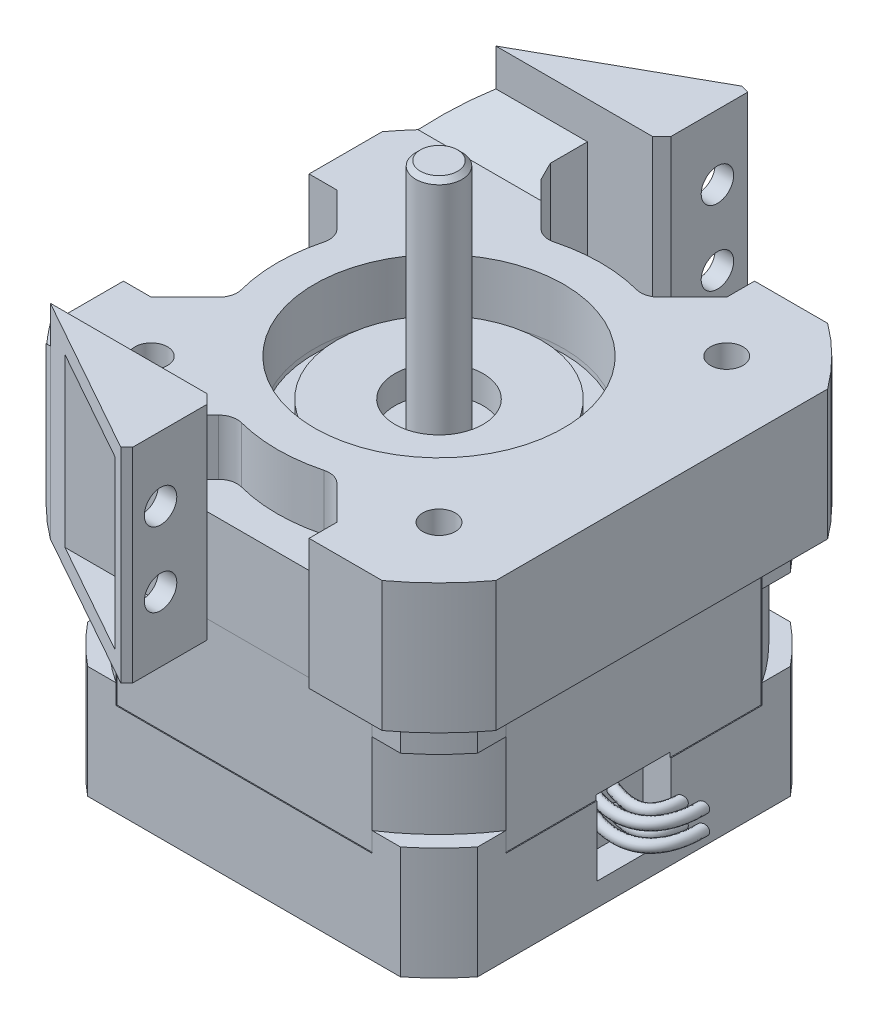
SolidWorks part; units mm, degrees
ref_plane "Front Plane" through (0, 0, 0) normal (0, 0, 1) x (1, 0, 0)
ref_plane "Top Plane" through (0, 0, 0) normal (0, 1, 0) x (1, 0, 0)
ref_plane "Right Plane" through (0, 0, 0) normal (1, 0, 0) x (0, 0, -1)
sketch "Sketch1" plane through (0, 0, 0) normal (0, 1, 0) x (1, 0, 0)
  line L0 (0, -21) -> (0, 21) construction
  line L1 (-21, 16.851) -> (-21, -16.851)
  line L2 (-16.851, -21) -> (16.851, -21)
  line L3 (21, -16.851) -> (21, 16.851)
  line L4 (16.851, 21) -> (-16.851, 21)
  line L5 (-21, 0) -> (21, 0) construction
  arc A0 (-21, 16.851) -> (-16.851, 21) centre (0, 0) cw
  arc A1 (16.851, 21) -> (21, 16.851) centre (0, 0) cw
  arc A2 (21, -16.851) -> (16.851, -21) centre (0, 0) cw
  arc A3 (-21, -16.851) -> (-16.851, -21) centre (0, 0) ccw
  dimension "D3" = 26.925
  dimension "D1" = 42
  dimension "D2" = 42
extrude "Boss-Extrude2" add sketch "Sketch1" along normal blind 33
sketch "Sketch3" plane through (0, 0, 0) normal (0, 0, 1) x (1, 0, 0)
  line L0 (0, -2.0131) -> (0, 34.8611) construction
  line L1 (-30.125, 20.875) -> (-25.125, 20.875)
  line L2 (-30.125, 20.875) -> (-30.125, 12.125)
  line L3 (-30.125, 12.125) -> (-25.125, 12.125)
  line L4 (-25.125, 20.875) -> (-25.125, 12.125)
  line L5 (21, 16.5) -> (-21, 16.5) construction
  line L6 (21, 33) -> (21, 0) construction
  line L7 (-21, 33) -> (-21, 0) construction
  point P13 (-25.125, 16.5)
  dimension "D1" = 8.75
  dimension "D2" = 25.125
  dimension "D3" = 5
revolve "Cut-Revolve1" cut sketch "Sketch3" angle 360 about L0
sketch "Sketch4" plane through (0, 33, 0) normal (0, 1, 0) x (1, 0, 0)
  circle A0 centre (0, 0) radius 13.425
  dimension "D1" = 26.85
extrude "Cut-Extrude1" cut sketch "Sketch4" against normal blind 0.5
sketch "Sketch5" plane through (0, 32.5, 0) normal (0, 1, 0) x (1, 0, 0)
  circle A0 centre (0, 0) radius 11
  dimension "D1" = 22
extrude "Boss-Extrude3" add sketch "Sketch5" along normal blind 2.5
sketch "Sketch6" plane through (0, 35, 0) normal (0, 1, 0) x (1, 0, 0)
  circle A0 centre (0, 0) radius 4.75
  dimension "D1" = 9.5
extrude "Cut-Extrude2" cut sketch "Sketch6" against normal blind 3
sketch "Sketch7" plane through (0, 32, 0) normal (0, 1, 0) x (1, 0, 0)
  circle A0 centre (0, 0) radius 2.5
  dimension "D1" = 5
extrude "Boss-Extrude4" add sketch "Sketch7" along normal blind 25.25
chamfer "Chamfer1" distance 0.5 angle 45 1 edges at (0, 57.25, 2.5)
sketch "Sketch8" plane through (0, 0, 0) normal (0, -1, 0) x (1, 0, 0)
  circle A0 centre (0, 0) radius 4.5
  dimension "D1" = 9
extrude "Cut-Extrude3" cut sketch "Sketch8" against normal blind 3
sketch "Sketch9" plane through (0, 33, 0) normal (0, 1, 0) x (1, 0, 0)
  line L0 (-15.5, 15.5) -> (15.5, 15.5) construction
  line L1 (15.5, 15.5) -> (15.5, -15.5) construction
  line L2 (15.5, -15.5) -> (-15.5, -15.5) construction
  line L3 (-15.5, -15.5) -> (-15.5, 15.5) construction
  point P2 (-15.5, 0)
  point P5 (0, 15.5)
  dimension "D1" = 31
  dimension "D2" = 31
hole_wizard "M3x0.5 Tapped Hole1" positions "Sketch11" profile "Sketch10" tap size "M3x0.5" standard "ANSI Metric"
sketch "Sketch11" plane through (0, 33, 0) normal (0, 1, 0) x (1, 0, 0)
  point P0 (-15.5, -15.5)
  point P3 (-15.5, 15.5)
  point P6 (15.5, 15.5)
  point P9 (15.5, -15.5)
sketch "Sketch10" plane through (-15.5, 33, 15.5) normal (1, 0, 0) x (0, 0, 1)
  line L0 (0, 0) -> (0, 5.2511)
  line L1 (0, 5.2511) -> (1.25, 4.5)
  line L2 (1.25, 4.5) -> (1.25, 0)
  line L5 (1.25, 0) -> (0, 0)
  line L10 (0, 5.2511) -> (-1.25, 4.5) construction
  line L11 (0, -6.35) -> (0, 107.95) construction
  dimension "Tap Drill Dia." = 2.5
  dimension "Tap Drill Depth" = 4.5
  dimension "Drill Angle" = 118
sketch "Sketch12" plane through (21, 0, 0) normal (1, 0, 0) x (0, 0, -1)
  line L0 (-16.851, 0) -> (16.851, 0) construction
  line L1 (-4, 10.5) -> (4, 10.5)
  line L2 (-4, 10.5) -> (-4, 2.5)
  line L3 (-4, 2.5) -> (4, 2.5)
  line L4 (4, 10.5) -> (4, 2.5)
  point P4 (0, 2.5)
  dimension "D1" = 8
  dimension "D2" = 8
  dimension "D3" = 2.5
extrude "Cut-Extrude4" cut sketch "Sketch12" against normal blind 3
sketch "Sketch13" plane through (18, 0, 0) normal (1, 0, 0) x (0, 0, -1)
  circle A0 centre (-1.1125, 7.415) radius 0.6
  circle A1 centre (0.707, 7.415) radius 0.6
  circle A2 centre (-1.1125, 5.3322) radius 0.6
  circle A3 centre (0.707, 5.3322) radius 0.6
  dimension "D1" = 1.2
sketch "Sketch14" plane through (0, 0, 0) normal (0, 1, 0) x (1, 0, 0)
  spline S0 degree 2 poles (17.6767, 0) (23.6461, -2.3668) (23.7984, 3.3576) knots 0 0 0 1 1 1
sweep "Sweep2" add profiles "Sketch13" path "Sketch14"
sketch "Sketch15" plane through (0, 0, -21) normal (0, 0, -1) x (-1, 0, 0)
  line L0 (-13.7937, 12.125) -> (-13.7937, 20.875) construction
  line L1 (-13.7937, 23) -> (13.7937, 23)
  line L2 (-13.7937, 23) -> (-13.7937, 10)
  line L3 (-13.7937, 10) -> (13.7937, 10)
  line L4 (13.7937, 23) -> (13.7937, 10)
  line L5 (13.7937, 20.875) -> (13.7937, 12.125) construction
  point P8 (-13.7937, 16.5)
  point P9 (-13.7937, 16.5)
  dimension "D1" = 13
extrude "Cut-Extrude5" cut sketch "Sketch15" against normal blind 0.1
ref_axis "Axis1" through (0, 0, 0) along (0, 1, 0)
pattern_circular "CirPattern1" count 4 over 360 about axis through (0, 0, 0) along (0, 1, 0) of "Cut-Extrude5"
ref_plane "Plane1" through (0, 33, 0) normal (0, 1, 0) x (1, 0, 0)
sketch "Sketch16" plane through (0, 33, 0) normal (0, 1, 0) x (1, 0, 0)
  line L0 (-10.001, -21) -> (-5.5264, -16.5254)
  line L1 (9.999, -21) -> (5.5249, -16.5259)
  line L2 (-21, -9.999) -> (-16.5259, -5.5249)
  line L3 (-16.5254, 5.5264) -> (-21, 10.001)
  line L4 (-21, 16.851) -> (-21, -16.851)
  line L5 (-16.851, -21) -> (16.851, -21)
  line L6 (21, -16.851) -> (21, 16.851)
  line L7 (16.851, 21) -> (-16.851, 21)
  line L8 (-21, 16.851) -> (-21, -16.851)
  line L9 (-16.851, -21) -> (16.851, -21)
  line L10 (21, -16.851) -> (21, 16.851)
  line L11 (16.851, 21) -> (-16.851, 21)
  line L12 (-10.001, 21) -> (-5.5264, 16.5254)
  line L13 (9.999, 21) -> (5.5249, 16.5259)
  circle A0 centre (0, 0) radius 13.425 construction
  circle A1 centre (0, 0) radius 13.425
  arc A4 (-16.851, 21) -> (-21, 16.851) centre (0, 0) ccw
  arc A5 (-21, -16.851) -> (-16.851, -21) centre (0, 0) ccw
  arc A6 (16.851, -21) -> (21, -16.851) centre (0, 0) ccw
  arc A7 (21, 16.851) -> (16.851, 21) centre (0, 0) ccw
  arc A8 (-16.851, 21) -> (-21, 16.851) centre (0, 0) ccw
  arc A9 (-21, -16.851) -> (-16.851, -21) centre (0, 0) ccw
  arc A10 (16.851, -21) -> (21, -16.851) centre (0, 0) ccw
  arc A11 (21, 16.851) -> (16.851, 21) centre (0, 0) ccw
  circle A12 centre (-15.5, -15.5) radius 1.25 construction
  circle A13 centre (15.5, -15.5) radius 1.25 construction
  circle A14 centre (15.5, 15.5) radius 1.25 construction
  circle A15 centre (-15.5, 15.5) radius 1.25 construction
  circle A16 centre (-15.5, -15.5) radius 1.25
  circle A17 centre (15.5, -15.5) radius 1.25
  circle A18 centre (15.5, 15.5) radius 1.25
  circle A19 centre (-15.5, 15.5) radius 1.25
  circle A20 centre (-15.5, 15.5) radius 1.75
  circle A21 centre (-15.5, -15.5) radius 1.75
  circle A22 centre (15.5, -15.5) radius 1.75
  circle A23 centre (15.5, 15.5) radius 1.75
  circle A24 centre (0, 0) radius 17.425
  dimension "D4" = 20
  dimension "D5" = 45
  dimension "D6" = 45
  dimension "D7" = 6.85
  dimension "D8" = 45
  dimension "D9" = 45
  dimension "D10" = 20
  dimension "D11" = 6.85
  dimension "D12" = 45
  dimension "D13" = 45
  dimension "D14" = 20
  dimension "D15" = 6.85
  dimension "D1" = 0
  dimension "D2" = 0.5
  dimension "D3" = 4
extrude "Boss-Extrude5" add sketch "Sketch16" along normal blind 6 separate body contours A24 L2 L8 A9 L9 L0 A21 | A24 A1 | A24 L12 L11 A8 L8 L3 A20 | A24 L1 L9 A10 L10 A11 L11 L13 A23 A22 region at (-13.426, 33, 20.7812) region at (-11.9734, 33, 11.9723) region at (8.0785, 33, 18.4465) region at (-18.608, 33, -7.9184)
sketch "Sketch17" plane through (0, 39, 0) normal (0, 1, 0) x (1, 0, 0)
  line L13 (-21, 10.001) -> (-24, 10.001)
  line L14 (-10.001, 21) -> (-10.001, 24)
  line L15 (9.999, 21) -> (9.999, 24)
  line L16 (-21, -9.999) -> (-24, -9.999)
  line L17 (-10.001, -21) -> (-10.001, -24)
  line L18 (9.999, -21) -> (9.999, -24)
  line L26 (-8.7583, -24) -> (-4.6476, -19.8892)
  line L27 (4.646, -19.8896) -> (8.7564, -24)
  line L28 (8.7564, -24) -> (17.8747, -24)
  line L29 (24, -17.8747) -> (24, 17.8747)
  line L30 (17.8747, 24) -> (8.7564, 24)
  line L31 (8.7564, 24) -> (4.646, 19.8896)
  line L32 (-4.6476, 19.8892) -> (-8.7583, 24)
  line L33 (-8.7583, 24) -> (-17.8747, 24)
  line L34 (-24, 17.8747) -> (-24, 8.7583)
  line L35 (-24, 8.7583) -> (-19.8892, 4.6476)
  line L36 (-19.8896, -4.646) -> (-24, -8.7564)
  line L37 (-24, -8.7564) -> (-24, -17.8747)
  line L38 (-17.8747, -24) -> (-8.7583, -24)
  line L39 (-8.7583, -24) -> (-4.6476, -19.8892)
  line L40 (4.646, -19.8896) -> (8.7564, -24)
  line L41 (8.7564, -24) -> (17.8747, -24)
  line L42 (24, -17.8747) -> (24, 17.8747)
  line L43 (17.8747, 24) -> (8.7564, 24)
  line L44 (8.7564, 24) -> (4.646, 19.8896)
  line L45 (-4.6476, 19.8892) -> (-8.7583, 24)
  line L46 (-8.7583, 24) -> (-17.8747, 24)
  line L47 (-24, 17.8747) -> (-24, 8.7583)
  line L48 (-24, 8.7583) -> (-19.8892, 4.6476)
  line L49 (-19.8896, -4.646) -> (-24, -8.7564)
  line L50 (-24, -8.7564) -> (-24, -17.8747)
  line L51 (-17.8747, -24) -> (-8.7583, -24)
  line L71 (-9.7939, -21.5) -> (-5.3895, -17.0956)
  line L72 (5.388, -17.0961) -> (9.7919, -21.5)
  line L73 (9.7919, -21.5) -> (17.0259, -21.5)
  line L74 (21.5, -17.0259) -> (21.5, 17.0259)
  line L75 (17.0259, 21.5) -> (9.7919, 21.5)
  line L76 (9.7919, 21.5) -> (5.388, 17.0961)
  line L77 (-5.3895, 17.0956) -> (-9.7939, 21.5)
  line L78 (-9.7939, 21.5) -> (-17.0259, 21.5)
  line L79 (-21.5, 17.0259) -> (-21.5, 9.7939)
  line L80 (-21.5, 9.7939) -> (-17.0956, 5.3895)
  line L81 (-17.0961, -5.388) -> (-21.5, -9.7919)
  line L82 (-21.5, -9.7919) -> (-21.5, -17.0259)
  line L83 (-17.0259, -21.5) -> (-9.7939, -21.5)
  line L84 (-9.7939, -21.5) -> (-5.3895, -17.0956)
  line L85 (5.388, -17.0961) -> (9.7919, -21.5)
  line L86 (9.7919, -21.5) -> (17.0259, -21.5)
  line L87 (21.5, -17.0259) -> (21.5, 17.0259)
  line L88 (17.0259, 21.5) -> (9.7919, 21.5)
  line L89 (9.7919, 21.5) -> (5.388, 17.0961)
  line L90 (-5.3895, 17.0956) -> (-9.7939, 21.5)
  line L91 (-9.7939, 21.5) -> (-17.0259, 21.5)
  line L92 (-21.5, 17.0259) -> (-21.5, 9.7939)
  line L93 (-21.5, 9.7939) -> (-17.0956, 5.3895)
  line L94 (-17.0961, -5.388) -> (-21.5, -9.7919)
  line L95 (-21.5, -9.7919) -> (-21.5, -17.0259)
  line L96 (-17.0259, -21.5) -> (-9.7939, -21.5)
  arc A14 (-4.6476, -19.8892) -> (4.646, -19.8896) centre (0, 0) ccw
  arc A15 (17.8747, -24) -> (24, -17.8747) centre (0, 0) ccw
  arc A16 (24, 17.8747) -> (17.8747, 24) centre (0, 0) ccw
  arc A17 (4.646, 19.8896) -> (-4.6476, 19.8892) centre (0, 0) ccw
  arc A18 (-17.8747, 24) -> (-24, 17.8747) centre (0, 0) ccw
  arc A19 (-19.8892, 4.6476) -> (-19.8896, -4.646) centre (0, 0) ccw
  arc A20 (-24, -17.8747) -> (-17.8747, -24) centre (0, 0) ccw
  arc A21 (-4.6476, -19.8892) -> (4.646, -19.8896) centre (0, 0) ccw
  arc A22 (17.8747, -24) -> (24, -17.8747) centre (0, 0) ccw
  arc A23 (24, 17.8747) -> (17.8747, 24) centre (0, 0) ccw
  arc A24 (4.646, 19.8896) -> (-4.6476, 19.8892) centre (0, 0) ccw
  arc A25 (-17.8747, 24) -> (-24, 17.8747) centre (0, 0) ccw
  arc A26 (-19.8892, 4.6476) -> (-19.8896, -4.646) centre (0, 0) ccw
  arc A27 (-24, -17.8747) -> (-17.8747, -24) centre (0, 0) ccw
  arc A36 (-5.3895, -17.0956) -> (5.388, -17.0961) centre (0, 0) ccw
  arc A37 (17.0259, -21.5) -> (21.5, -17.0259) centre (0, 0) ccw
  arc A38 (21.5, 17.0259) -> (17.0259, 21.5) centre (0, 0) ccw
  arc A39 (5.388, 17.0961) -> (-5.3895, 17.0956) centre (0, 0) ccw
  arc A40 (-17.0259, 21.5) -> (-21.5, 17.0259) centre (0, 0) ccw
  arc A41 (-17.0956, 5.3895) -> (-17.0961, -5.388) centre (0, 0) ccw
  arc A42 (-21.5, -17.0259) -> (-17.0259, -21.5) centre (0, 0) ccw
  arc A43 (-5.3895, -17.0956) -> (5.388, -17.0961) centre (0, 0) ccw
  arc A44 (17.0259, -21.5) -> (21.5, -17.0259) centre (0, 0) ccw
  arc A45 (21.5, 17.0259) -> (17.0259, 21.5) centre (0, 0) ccw
  arc A46 (5.388, 17.0961) -> (-5.3895, 17.0956) centre (0, 0) ccw
  arc A47 (-17.0259, 21.5) -> (-21.5, 17.0259) centre (0, 0) ccw
  arc A48 (-17.0956, 5.3895) -> (-17.0961, -5.388) centre (0, 0) ccw
  arc A49 (-21.5, -17.0259) -> (-17.0259, -21.5) centre (0, 0) ccw
  line M24 (9.999, -21) -> (16.851, -21)
  arc M25 (16.851, -21) -> (21, -16.851) centre (0, 0) ccw
  line M26 (21, -16.851) -> (21, 16.851)
  arc M27 (21, 16.851) -> (16.851, 21) centre (0, 0) ccw
  line M28 (16.851, 21) -> (9.999, 21)
  line M32 (-10.001, 21) -> (-16.851, 21)
  arc M33 (-16.851, 21) -> (-21, 16.851) centre (0, 0) ccw
  line M34 (-21, 16.851) -> (-21, 10.001)
  line M38 (-21, -9.999) -> (-21, -16.851)
  arc M39 (-21, -16.851) -> (-16.851, -21) centre (0, 0) ccw
  line M40 (-16.851, -21) -> (-10.001, -21)
  dimension "D1" = 3
  dimension "D2" = 0.5
extrude "Boss-Extrude6" add sketch "Sketch17" against normal blind 14 separate body contours L46 A25 L47 L13 L14 M34 M33 M32 | L50 A27 L51 L17 L16 M40 M39 M38 | L42 A23 L43 L15 L18 L41 A22 M28 M27 M26 M25 M24 region at (-22.75, 39, -10.199) region at (-21.698, 39, 13.5124) region at (10.499, 39, -22.75)
fillet "Fillet1" radius 2 6 edges at (5.5249, 36, 16.5259) (-5.5264, 36, 16.5254) (-16.5259, 36, 5.5249) (-16.5254, 36, -5.5264) (5.5249, 36, -16.5259) (-5.5264, 36, -16.5254)
extrude "Boss-Extrude7" add sketch "Sketch17<4>" against normal up to vertex (6 mm away) separate body contours L95 A49 L96 L17 L16 M40 M39 M38 | L91 A47 L92 L13 L14 M34 M33 M32 | L87 A45 L88 L15 L18 L86 A44 M28 M27 M26 M25 M24 region at (-21.25, 39, -10.1636) region at (-21.25, 39, 10.1617) region at (13.5124, 39, -21.0549) up to point (-17.3686, 33, 6.3676)
sketch "Sketch17<4>" plane through (0, 39, 0) normal (0, 1, 0) x (1, 0, 0) same geometry as "Sketch17"
combine bodies "Combine2" operation type add bodies to combine 115 122 121 114 116 117 120
sketch "Sketch18" plane through (0, 39, 0) normal (0, 1, 0) x (1, 0, 0)
  line L0 (-10.001, 24) -> (-0.001, 24)
  line L1 (-0.001, 24) -> (-0.001, 34)
  line L3 (-17.8747, 24) -> (-0.001, 34)
  line L4 (-17.8747, -24) -> (-0.001, -24)
  line L5 (-10.001, -21) -> (-10.001, -24) construction
  line L6 (-0.001, -24) -> (-0.001, -34)
  line L7 (-0.001, -34) -> (-17.8747, -24)
  line L23 (9.999, 24) -> (9.999, 21)
  line L24 (9.999, 21) -> (6.3676, 17.3686)
  line L25 (-6.3692, 17.3682) -> (-10.001, 21)
  line L26 (-10.001, 21) -> (-10.001, 24)
  line L27 (-10.001, 24) -> (-17.8747, 24)
  line L28 (-24, 17.8747) -> (-24, 10.001)
  line L29 (-24, 10.001) -> (-21, 10.001)
  line L30 (-21, 10.001) -> (-17.3682, 6.3692)
  line L31 (-17.3686, -6.3676) -> (-21, -9.999)
  line L32 (-21, -9.999) -> (-24, -9.999)
  line L33 (-24, -9.999) -> (-24, -17.8747)
  line L34 (-17.8747, -24) -> (-10.001, -24)
  line L35 (-10.001, -24) -> (-10.001, -21)
  line L36 (-10.001, -21) -> (-6.3692, -17.3682)
  line L37 (6.3676, -17.3686) -> (9.999, -21)
  line L38 (9.999, -21) -> (9.999, -24)
  line L39 (9.999, -24) -> (17.8747, -24)
  line L40 (24, -17.8747) -> (24, 17.8747)
  line L41 (17.8747, 24) -> (9.999, 24)
  line L46 (-10.001, 24) -> (-17.8747, 24)
  arc A15 (4.4434, 16.8489) -> (6.3676, 17.3686) centre (4.9534, 18.7828) ccw
  arc A16 (4.4434, 16.8489) -> (-4.4448, 16.8486) centre (0, 0) ccw
  arc A17 (-6.3692, 17.3682) -> (-4.4448, 16.8486) centre (-4.955, 18.7824) ccw
  arc A18 (-17.8747, 24) -> (-24, 17.8747) centre (0, 0) ccw
  arc A19 (-16.8486, 4.4448) -> (-17.3682, 6.3692) centre (-18.7824, 4.955) ccw
  arc A20 (-16.8486, 4.4448) -> (-16.8489, -4.4434) centre (0, 0) ccw
  arc A21 (-17.3686, -6.3676) -> (-16.8489, -4.4434) centre (-18.7828, -4.9534) ccw
  arc A22 (-24, -17.8747) -> (-17.8747, -24) centre (0, 0) ccw
  arc A23 (-4.4448, -16.8486) -> (-6.3692, -17.3682) centre (-4.955, -18.7824) ccw
  arc A24 (-4.4448, -16.8486) -> (4.4434, -16.8489) centre (0, 0) ccw
  arc A25 (6.3676, -17.3686) -> (4.4434, -16.8489) centre (4.9534, -18.7828) ccw
  arc A26 (17.8747, -24) -> (24, -17.8747) centre (0, 0) ccw
  arc A27 (24, 17.8747) -> (17.8747, 24) centre (0, 0) ccw
  dimension "D3" = 10
  dimension "D1" = 10
  dimension "D2" = 10
  dimension "D4" = 10
  dimension "D5" = 0
extrude "Boss-Extrude8" add sketch "Sketch18" against normal up to surface (14 mm away) up to face at (-18.2819, 25, -18.2819)
sketch "Sketch19" plane through (-0.001, 0, 0) normal (1, 0, 0) x (0, 0, -1)
  line L0 (34, 25) -> (34, 39) construction
  line L1 (34, 27) -> (26, 27)
  line L2 (34, 27) -> (34, 37)
  line L3 (34, 37) -> (26, 37)
  line L4 (26, 27) -> (26, 37)
  line L5 (24, 39) -> (34, 39) construction
  line L6 (-34, 25) -> (-34, 39) construction
  line L7 (-34, 37) -> (-26, 37)
  line L8 (-34, 37) -> (-34, 27)
  line L9 (-34, 27) -> (-26, 27)
  line L10 (-26, 37) -> (-26, 27)
  line L11 (-34, 39) -> (-24, 39) construction
  circle A0 centre (30, 32) radius 1.75
  circle A1 centre (-30, 32) radius 1.75
  point P19 (34, 32)
  point P20 (-34, 32)
  point P21 (30, 27)
  point P25 (-30, 27)
  dimension "D7" = 3.5
  dimension "D8" = 3.5
  dimension "D1" = 10
  dimension "D2" = 2
  dimension "D3" = 8
  dimension "D4" = 8
  dimension "D5" = 10
  dimension "D6" = 2
ref_plane "Plane2" through (-2.001, 0, 0) normal (1, 0, 0) x (0, 0, -1)
sketch "Sketch20" plane through (-2.001, 0, 0) normal (1, 0, 0) x (0, 0, -1)
  line L0 (34, 27) -> (34, 37) construction
  line L1 (34, 37) -> (26, 37) construction
  line L2 (34, 27) -> (26, 27) construction
  line L3 (26, 27) -> (26, 37) construction
  line L4 (-34, 37) -> (-34, 27) construction
  line L5 (-34, 37) -> (-26, 37) construction
  line L6 (-26, 37) -> (-26, 27) construction
  line L7 (-34, 27) -> (-26, 27) construction
  line L8 (34, 27) -> (34, 37)
  line L9 (34, 37) -> (26, 37)
  line L10 (34, 27) -> (26, 27)
  line L11 (26, 27) -> (26, 37)
  line L12 (-34, 37) -> (-34, 27)
  line L13 (-34, 37) -> (-26, 37)
  line L14 (-26, 37) -> (-26, 27)
  line L15 (-34, 27) -> (-26, 27)
  circle A0 centre (-30, 32) radius 1.75 construction
  circle A1 centre (30, 32) radius 1.75 construction
  circle A2 centre (-30, 32) radius 1.75
  circle A3 centre (30, 32) radius 1.75
extrude "Cut-Extrude7" cut sketch "Sketch20" against normal blind 34 contours L12 L15 L14 L13 A2 | A2 | L10 L11 L9 L8 region at (-2.001, 36.8719, 30)
chamfer "Chamfer2" distance 2 angle 45 2 edges at (-10.001, 32, 24) (-10.001, 32, -24)
ref_plane "Plane3" [suppressed] through (-2.001, 37, 32.881) normal (0, 0, 1) x (1, 0, 0)
extrude "Cut-Extrude10" cut sketch "Sketch19" against normal blind 10 contours A0 | A1
sketch "Sketch21" plane through (0, 39, 0) normal (0, 1, 0) x (1, 0, 0)
  line L0 (-17.8747, -24) -> (-8.001, -24)
  line L1 (-8.001, 24) -> (-17.8747, 24)
  line L25 (9.999, 24) -> (9.999, 21)
  line L26 (9.999, 21) -> (6.3676, 17.3686)
  line L27 (-6.3692, 17.3682) -> (-10.001, 21)
  line L28 (-10.001, 21) -> (-10.001, 22)
  line L29 (-10.001, 22) -> (-8.001, 24)
  line L30 (-8.001, 24) -> (-0.001, 24)
  line L31 (-0.001, 24) -> (-0.001, 34)
  line L32 (-0.001, 34) -> (-17.8747, 24)
  line L33 (-24, 17.8747) -> (-24, 10.001)
  line L34 (-24, 10.001) -> (-21, 10.001)
  line L35 (-21, 10.001) -> (-17.3682, 6.3692)
  line L36 (-17.3686, -6.3676) -> (-21, -9.999)
  line L37 (-21, -9.999) -> (-24, -9.999)
  line L38 (-24, -9.999) -> (-24, -17.8747)
  line L39 (-17.8747, -24) -> (-0.001, -34)
  line L40 (-0.001, -34) -> (-0.001, -24)
  line L41 (-0.001, -24) -> (-8.001, -24)
  line L42 (-8.001, -24) -> (-10.001, -22)
  line L43 (-10.001, -22) -> (-10.001, -21)
  line L44 (-10.001, -21) -> (-6.3692, -17.3682)
  line L45 (6.3676, -17.3686) -> (9.999, -21)
  line L46 (9.999, -21) -> (9.999, -24)
  line L47 (9.999, -24) -> (17.8747, -24)
  line L48 (24, -17.8747) -> (24, 17.8747)
  line L49 (17.8747, 24) -> (9.999, 24)
  line L50 (9.999, 24) -> (9.999, 21)
  line L51 (9.999, 21) -> (6.3676, 17.3686)
  line L52 (-6.3692, 17.3682) -> (-10.001, 21)
  line L53 (-10.001, 21) -> (-10.001, 22)
  line L54 (-10.001, 22) -> (-8.001, 24)
  line L55 (-8.001, 24) -> (-0.001, 24)
  line L56 (-0.001, 24) -> (-0.001, 34)
  line L57 (-0.001, 34) -> (-17.8747, 24)
  line L58 (-24, 17.8747) -> (-24, 10.001)
  line L59 (-24, 10.001) -> (-21, 10.001)
  line L60 (-21, 10.001) -> (-17.3682, 6.3692)
  line L61 (-17.3686, -6.3676) -> (-21, -9.999)
  line L62 (-21, -9.999) -> (-24, -9.999)
  line L63 (-24, -9.999) -> (-24, -17.8747)
  line L64 (-17.8747, -24) -> (-0.001, -34)
  line L65 (-0.001, -34) -> (-0.001, -24)
  line L66 (-0.001, -24) -> (-8.001, -24)
  line L67 (-8.001, -24) -> (-10.001, -22)
  line L68 (-10.001, -22) -> (-10.001, -21)
  line L69 (-10.001, -21) -> (-6.3692, -17.3682)
  line L70 (6.3676, -17.3686) -> (9.999, -21)
  line L71 (9.999, -21) -> (9.999, -24)
  line L72 (9.999, -24) -> (17.8747, -24)
  line L73 (24, -17.8747) -> (24, 17.8747)
  line L74 (17.8747, 24) -> (9.999, 24)
  arc A13 (4.4434, 16.8489) -> (6.3676, 17.3686) centre (4.9534, 18.7828) ccw
  arc A14 (4.4434, 16.8489) -> (-4.4448, 16.8486) centre (0, 0) ccw
  arc A15 (-6.3692, 17.3682) -> (-4.4448, 16.8486) centre (-4.955, 18.7824) ccw
  arc A16 (-17.8747, 24) -> (-24, 17.8747) centre (0, 0) ccw
  arc A17 (-16.8486, 4.4448) -> (-17.3682, 6.3692) centre (-18.7824, 4.955) ccw
  arc A18 (-16.8486, 4.4448) -> (-16.8489, -4.4434) centre (0, 0) ccw
  arc A19 (-17.3686, -6.3676) -> (-16.8489, -4.4434) centre (-18.7828, -4.9534) ccw
  arc A20 (-24, -17.8747) -> (-17.8747, -24) centre (0, 0) ccw
  arc A21 (-4.4448, -16.8486) -> (-6.3692, -17.3682) centre (-4.955, -18.7824) ccw
  arc A22 (-4.4448, -16.8486) -> (4.4434, -16.8489) centre (0, 0) ccw
  arc A23 (6.3676, -17.3686) -> (4.4434, -16.8489) centre (4.9534, -18.7828) ccw
  arc A24 (17.8747, -24) -> (24, -17.8747) centre (0, 0) ccw
  arc A25 (24, 17.8747) -> (17.8747, 24) centre (0, 0) ccw
  arc A26 (4.4434, 16.8489) -> (6.3676, 17.3686) centre (4.9534, 18.7828) ccw
  arc A27 (4.4434, 16.8489) -> (-4.4448, 16.8486) centre (0, 0) ccw
  arc A28 (-6.3692, 17.3682) -> (-4.4448, 16.8486) centre (-4.955, 18.7824) ccw
  arc A29 (-17.8747, 24) -> (-24, 17.8747) centre (0, 0) ccw
  arc A30 (-16.8486, 4.4448) -> (-17.3682, 6.3692) centre (-18.7824, 4.955) ccw
  arc A31 (-16.8486, 4.4448) -> (-16.8489, -4.4434) centre (0, 0) ccw
  arc A32 (-17.3686, -6.3676) -> (-16.8489, -4.4434) centre (-18.7828, -4.9534) ccw
  arc A33 (-24, -17.8747) -> (-17.8747, -24) centre (0, 0) ccw
  arc A34 (-4.4448, -16.8486) -> (-6.3692, -17.3682) centre (-4.955, -18.7824) ccw
  arc A35 (-4.4448, -16.8486) -> (4.4434, -16.8489) centre (0, 0) ccw
  arc A36 (6.3676, -17.3686) -> (4.4434, -16.8489) centre (4.9534, -18.7828) ccw
  arc A37 (17.8747, -24) -> (24, -17.8747) centre (0, 0) ccw
  arc A38 (24, 17.8747) -> (17.8747, 24) centre (0, 0) ccw
  line M47 (-8.001, 24) -> (-0.001, 24)
  line M48 (-0.001, 24) -> (-0.001, 34)
  line M49 (-0.001, 34) -> (-17.8747, 24)
  line M61 (-17.8747, -24) -> (-0.001, -34)
  line M62 (-0.001, -34) -> (-0.001, -24)
  line M63 (-0.001, -24) -> (-8.001, -24)
  dimension "D1" = 0
extrude "Boss-Extrude9" add sketch "Sketch21" along normal blind 8 contours L0 M61 M62 M63 | L1 M47 M48 M49 region at (-5.9589, 39, 27.3333) region at (-5.9589, 39, -27.3333)
sketch "Sketch22" plane through (0, 37, 0) normal (0, -1, 0) x (1, 0, 0)
  line L0 (-14.3, -26) -> (-2.001, -32.881) construction
  line L1 (-2.001, -32.881) -> (-2.001, -26) construction
  line L2 (-2.001, -26) -> (-14.3, -26) construction
  line L3 (-14.3, 26) -> (-2.001, 26) construction
  line L4 (-2.001, 26) -> (-2.001, 32.881) construction
  line L5 (-2.001, 32.881) -> (-14.3, 26) construction
  line L6 (-14.3, -26) -> (-2.001, -32.881)
  line L7 (-2.001, -32.881) -> (-2.001, -26)
  line L8 (-2.001, -26) -> (-14.3, -26)
  line L9 (-14.3, 26) -> (-2.001, 26)
  line L10 (-2.001, 26) -> (-2.001, 32.881)
  line L11 (-2.001, 32.881) -> (-14.3, 26)
extrude "Cut-Extrude11" cut sketch "Sketch22" against normal blind 8
sketch "Sketch23" plane through (-2.001, 0, 0) normal (-1, 0, 0) x (0, 0, 1)
  line L0 (26, 45) -> (32.881, 45) construction
  line L1 (26, 45) -> (26, 27) construction
  line L2 (-32.881, 45) -> (-26, 45) construction
  line L3 (-26, 27) -> (-26, 45) construction
  circle A0 centre (30, 40) radius 1.75
  circle A3 centre (-30, 40) radius 1.75
  dimension "D1" = 5
  dimension "D2" = 4
  dimension "D3" = 3.5
  dimension "D4" = 3.5
  dimension "D5" = 5
  dimension "D6" = 4
extrude "Cut-Extrude13" cut sketch "Sketch23" against normal up to surface (2 mm away) up to face at (-0.001, 32, -31.75)
chamfer "Chamfer3" distance 4 angle 45 2 edges at (-12.9379, 39, -24) (-12.9379, 39, 24)
chamfer "Chamfer4" distance 1 angle 45 4 edges at (-0.001, 36, -34) (-0.001, 36, 34) (-0.001, 36, -24) (-0.001, 36, 24) first distance on face at (-8.1505, 36, -29.4405) first distance on face at (-0.001, 40, 28.25) first distance on face at (-0.001, 40, -31.75)
